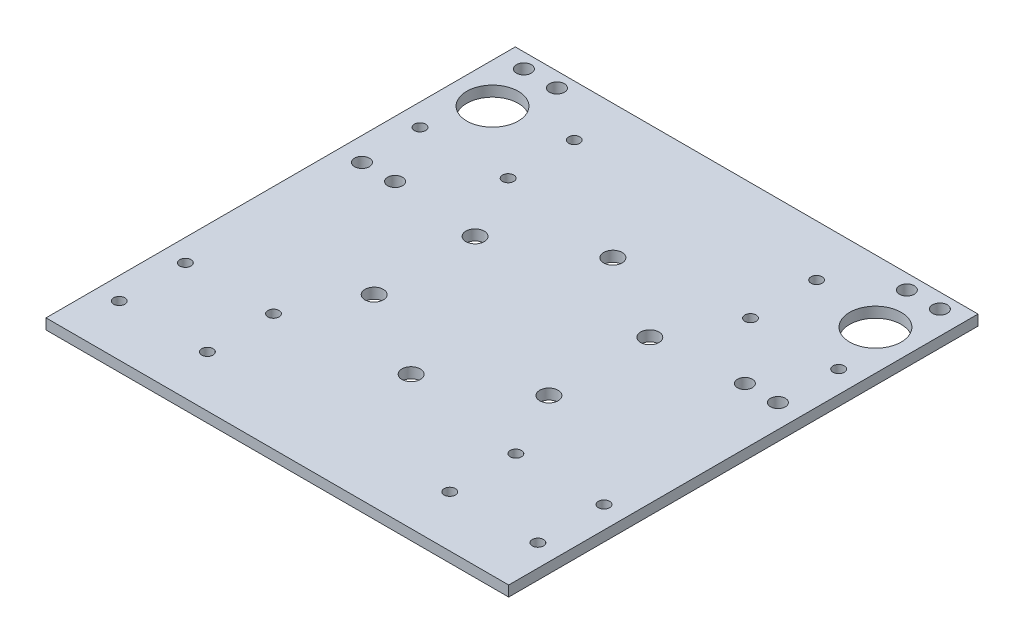
SolidWorks part; units mm, degrees
material "1060 Alloy"
ref_plane "Front Plane" through (0, 0, 0) normal (0, 0, 1) x (1, 0, 0)
ref_plane "Top Plane" through (0, 0, 0) normal (0, 1, 0) x (1, 0, 0)
ref_plane "Right Plane" through (0, 0, 0) normal (1, 0, 0) x (0, 0, -1)
sketch "Sketch1" plane through (0, 0, 0) normal (0, 1, 0) x (1, 0, 0)
  line L1 (-70, -71) -> (70, -71)
  line L2 (-70, -71) -> (-70, 71)
  line L3 (-70, 71) -> (70, 71)
  line L4 (70, -71) -> (70, 71)
  line L5 (-70, -71) -> (70, 71) construction
  line L6 (-70, 71) -> (70, -71) construction
  point P0 (0, 0)
  dimension "D1" = 140
  dimension "D2" = 142
extrude "Boss-Extrude1" add sketch "Sketch1" along normal blind 3.175
sketch "Sketch2" plane through (0, 3.175, 0) normal (0, 1, 0) x (1, 0, 0)
  line L0 (-45, 30.5) -> (-30, 30.5) construction
  line L1 (-45, -30.5) -> (45, -30.5) construction
  line L2 (-45, -30.5) -> (-45, 30.5) construction
  line L3 (-45, 30.5) -> (45, 30.5) construction
  line L4 (45, -30.5) -> (45, 30.5) construction
  line L5 (-45, -30.5) -> (45, 30.5) construction
  line L6 (-45, 30.5) -> (45, -30.5) construction
  line L7 (-30, 30.5) -> (-30, 60.5) construction
  line L8 (-70, 71) -> (-70, -71) construction
  line L9 (-30, 60.5) -> (-70, 60.5) construction
  line L10 (-30, 60.5) -> (-30, 30.5) construction
  line L11 (-30, 30.5) -> (-70, 30.5) construction
  line L12 (-70, 60.5) -> (-70, 30.5) construction
  line L13 (-30, 60.5) -> (-70, 30.5) construction
  line L14 (-30, 30.5) -> (-70, 60.5) construction
  line L15 (-51.4643, -23.9643) -> (-51.4643, 60.5) construction
  line L16 (-70, 45.5) -> (-30, 45.5) construction
  line L17 (-50, 60.5) -> (-50, 30.5) construction
  line L18 (-57.9286, 52.0357) -> (-57.9286, 62.0357) construction
  line L19 (-62.9286, 66.5357) -> (-52.9286, 66.5357) construction
  line L20 (-67.9286, 62.0357) -> (-47.9286, 62.0357) construction
  line L21 (-67.9286, 62.0357) -> (-67.9286, 22.0357) construction
  line L22 (-67.9286, 22.0357) -> (-47.9286, 22.0357) construction
  line L23 (-47.9286, 62.0357) -> (-47.9286, 22.0357) construction
  line L24 (-67.9286, 62.0357) -> (-47.9286, 22.0357) construction
  line L25 (-67.9286, 22.0357) -> (-47.9286, 62.0357) construction
  line L26 (-67.9286, 17.5357) -> (-47.9286, 17.5357) construction
  line L27 (-67.9286, 17.5357) -> (-67.9286, 66.5357) construction
  line L28 (-67.9286, 66.5357) -> (-47.9286, 66.5357) construction
  line L29 (-47.9286, 17.5357) -> (-47.9286, 66.5357) construction
  line L30 (-67.9286, 17.5357) -> (-47.9286, 66.5357) construction
  line L31 (-67.9286, 66.5357) -> (-47.9286, 17.5357) construction
  line L32 (-67.9286, 14.0357) -> (-47.9286, 14.0357) construction
  line L33 (-67.9286, 14.0357) -> (-67.9286, 70.0357) construction
  line L34 (-67.9286, 70.0357) -> (-47.9286, 70.0357) construction
  line L35 (-47.9286, 14.0357) -> (-47.9286, 70.0357) construction
  line L36 (-67.9286, 14.0357) -> (-47.9286, 70.0357) construction
  line L37 (-67.9286, 70.0357) -> (-47.9286, 14.0357) construction
  line L38 (-67.9286, 42.0357) -> (-47.9286, 42.0357) construction
  line L39 (0, -1.7463) -> (0, 1.7463) construction
  line L40 (-45, 30.5) -> (-45, 45.5) construction
  line L41 (-1.7463, 0) -> (1.7463, 0) construction
  line L42 (-67.9286, 52.0357) -> (-30, 52.0357) construction
  circle A0 centre (-45, 0) radius 6.4643 construction
  circle A1 centre (-57.9286, 52.0357) radius 6.4643 construction
  circle A2 centre (-57.9286, 52.0357) radius 7.8
  circle A8 centre (-57.9286, 52.0357) radius 2.45 construction
  circle A9 centre (-62.9286, 66.5357) radius 2.25
  circle A10 centre (-52.9286, 66.5357) radius 2.25
  circle A11 centre (-52.9286, 17.5357) radius 2.25
  circle A12 centre (-62.9286, 17.5357) radius 2.25
  circle A13 centre (52.9286, 17.5357) radius 2.25
  circle A14 centre (62.9286, 17.5357) radius 2.25
  circle A15 centre (57.9286, 52.0357) radius 7.8
  circle A16 centre (52.9286, 66.5357) radius 2.25
  circle A17 centre (62.9286, 66.5357) radius 2.25
  circle A18 centre (-36.6667, 55.5) radius 1.7
  circle A19 centre (-36.6667, 35.5) radius 1.7
  circle A20 centre (-63.3333, 35.5) radius 1.7
  circle A21 centre (-63.3333, 55.5) radius 1.7 construction
  circle A22 centre (36.6667, 35.5) radius 1.7
  circle A23 centre (63.3333, 35.5) radius 1.7
  circle A24 centre (36.6667, 55.5) radius 1.7
  circle A25 centre (63.3333, 55.5) radius 1.7 construction
  circle A26 centre (63.3333, -35.5) radius 1.7
  circle A27 centre (36.6667, -35.5) radius 1.7
  circle A28 centre (63.3333, -55.5) radius 1.7
  circle A29 centre (36.6667, -55.5) radius 1.7
  circle A30 centre (-36.6667, -35.5) radius 1.7
  circle A31 centre (-63.3333, -35.5) radius 1.7
  circle A32 centre (-36.6667, -55.5) radius 1.7
  circle A33 centre (-63.3333, -55.5) radius 1.7
  point P0 (0, 0)
  point P10 (-50, 45.5)
  point P25 (-57.9286, 42.0357)
  point P31 (-57.9286, 42.0357)
  point P32 (-57.9286, 62.0357)
  point P37 (-57.9286, 42.0357)
  point P44 (-57.9286, 66.5357)
  point P45 (-57.9286, 66.5357)
  dimension "D5" = 12.9286
  dimension "D6" = 12.9286
  dimension "D7" = 15.6
  dimension "D8" = 4.9
  dimension "D14" = 10
  dimension "D9" = 10
  dimension "4.5" = 4.5
  dimension "D16" = 3.4
  dimension "D1" = 90
  dimension "D2" = 61
  dimension "D3" = 15
  dimension "D4" = 30
  dimension "D10" = 20
  dimension "D11" = 40
  dimension "D12" = 49
  dimension "D13" = 56
  dimension "D17" = 5
  dimension "D18" = 8.4643
sketch "Sketch4" plane through (0, 3.175, 0) normal (0, 1, 0) x (1, 0, 0)
  line L0 (0, 0) -> (0, 30.525) construction
  line L1 (0, 0) -> (26.4354, 15.2625) construction
  circle A0 centre (0, 0) radius 40 construction
  circle A1 centre (0, 0) radius 30.525 construction
  circle A2 centre (0, 30.525) radius 2.7781
  circle A3 centre (26.4354, 15.2625) radius 2.7781
  circle A4 centre (26.4354, -15.2625) radius 2.7781
  circle A5 centre (0, -30.525) radius 2.7781
  circle A6 centre (-26.4354, -15.2625) radius 2.7781
  circle A7 centre (-26.4354, 15.2625) radius 2.7781
  dimension "D1" = 80
  dimension "D2" = 61.05
  dimension "D3" = 5.5563
  dimension "D5" = 60
  dimension "D4" = 6
extrude "Cut-Extrude1" cut sketch "Sketch2" against normal up to surface (3.175 mm away) contours A9 | A10 | A18 | A2 | A19 | A20 | A11 | A12 | A16 | A17 | A24 | A15 | A23 | A22 | A13 | A14 | A31 | A30 | A33 | A32 | A27 | A26 | A29 | A28 up to face at (0, 0, 0)
extrude "Cut-Extrude2" cut sketch "Sketch4" against normal up to surface (3.175 mm away) contours A7 | A2 | A3 | A6 | A4 | A5 up to face at (57.9286, 0, -59.8357)
